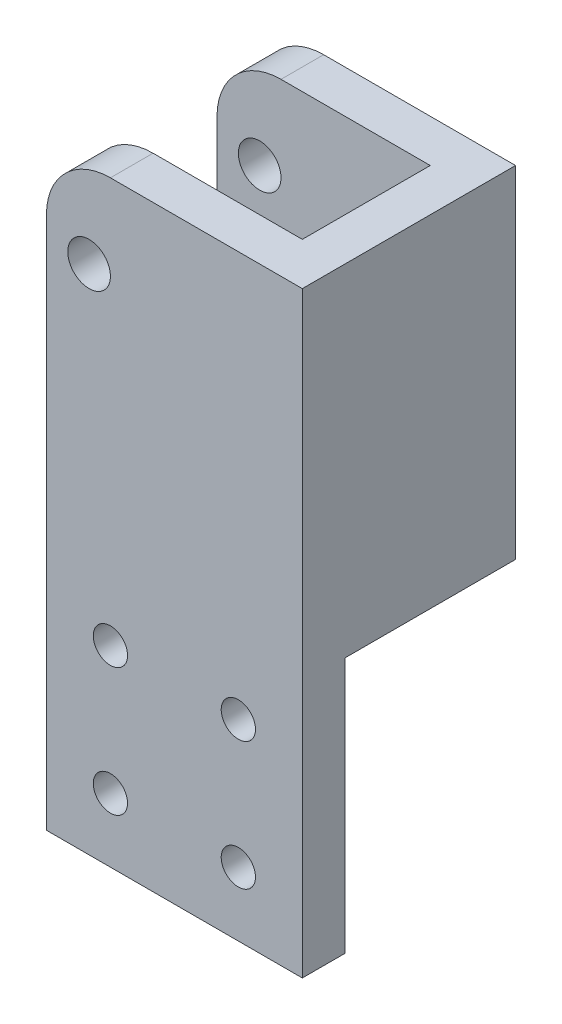
SolidWorks part; units mm, degrees
ref_plane "Front Plane" through (0, 0, 0) normal (0, 0, 1) x (1, 0, 0)
ref_plane "Top Plane" through (0, 0, 0) normal (0, 1, 0) x (1, 0, 0)
ref_plane "Right Plane" through (0, 0, 0) normal (1, 0, 0) x (0, 0, -1)
sketch "Sketch1" plane through (0, 0, 0) normal (0, 0, 1) x (1, 0, 0)
  line L1 (0, 0) -> (38.1, 0)
  line L2 (0, 0) -> (0, 76.2)
  line L3 (0, 76.2) -> (38.1, 76.2)
  line L4 (38.1, 0) -> (38.1, 76.2)
  dimension "D1" = 76.2
  dimension "D2" = 38.1
extrude "Boss-Extrude1" add sketch "Sketch1" against normal blind 31.75
sketch "Sketch2" plane through (0, 76.2, 0) normal (0, 1, 0) x (1, 0, 0)
  line L0 (0, 0) -> (0, 6.35)
  line L1 (0, 31.75) -> (0, 0) construction
  line L2 (0, 6.35) -> (31.75, 6.35)
  line L3 (31.75, 6.35) -> (31.75, 31.75)
  line L4 (38.1, 31.75) -> (0, 31.75) construction
  line L5 (38.1, 31.75) -> (38.1, 0) construction
  line L6 (31.75, 6.35) -> (31.75, 25.4) construction
  dimension "D1" = 6.35
  dimension "D2" = 6.35
  dimension "D3" = 19.05
sketch "Sketch3" plane through (0, 0, 0) normal (-1, 0, 0) x (0, 0, 1)
  line L0 (-31.75, 0) -> (-6.35, 0)
  line L1 (-31.75, 0) -> (0, 0) construction
  line L4 (-31.75, 0) -> (-31.75, 76.2)
  line L5 (-31.75, 76.2) -> (-6.35, 76.2)
  line L6 (-6.35, 0) -> (-6.35, 76.2)
  dimension "D1" = 25.4
  dimension "D2" = 76.2
extrude "Cut-Extrude2" cut sketch "Sketch3" against normal blind 31.75
sketch "Sketch4" plane through (31.75, 0, 0) normal (-1, 0, 0) x (0, 0, 1)
  line L0 (-6.35, 0) -> (-6.35, 76.2) construction
  line L1 (-31.75, 0) -> (-6.35, 0)
  line L2 (-31.75, 0) -> (-31.75, 25.4)
  line L3 (-31.75, 25.4) -> (-6.35, 25.4)
  line L4 (-6.35, 0) -> (-6.35, 25.4)
  dimension "D1" = 25.4
extrude "Cut-Extrude3" cut sketch "Sketch4" against normal through all
sketch "Sketch5" plane through (0, 76.2, 0) normal (0, 1, 0) x (1, 0, 0)
  line L0 (38.1, 31.75) -> (38.1, 0) construction
  line L1 (38.1, 0) -> (0, 0) construction
  line L2 (0, 0) -> (0, 6.35) construction
  line L3 (0, 6.35) -> (31.75, 6.35) construction
  line L4 (31.75, 6.35) -> (31.75, 31.75) construction
  line L5 (31.75, 31.75) -> (38.1, 31.75) construction
  line L6 (31.75, 6.35) -> (31.75, 25.4)
  line L7 (31.75, 31.75) -> (0, 31.75)
  line L8 (0, 31.75) -> (0, 25.4)
  line L9 (0, 25.4) -> (31.75, 25.4)
  line M6 (31.75, 31.75) -> (31.75, 6.35)
  dimension "D1" = 19.05
extrude "Boss-Extrude2" add sketch "Sketch5" against normal blind 50.8 contours L8 L9 L7 M6 region at (15.875, 76.2, -28.575)
sketch "Sketch6" plane through (0, 0, -31.75) normal (0, 0, -1) x (-1, 0, 0)
  line L0 (0, 76.2) -> (0, 63.5) construction
  line L1 (0, 25.4) -> (0, 76.2) construction
  line L2 (0, 63.5) -> (-6.35, 63.5) construction
  circle A0 centre (-6.35, 63.5) radius 3.175
  dimension "D3" = 6.35
  dimension "D1" = 12.7
  dimension "D2" = 6.35
extrude "Cut-Extrude4" cut sketch "Sketch6" against normal blind 50.8
fillet "Fillet2" radius 9.525 2 edges at (0, 76.2, -3.175) (0, 76.2, -28.575)
ref_plane "Plane1" through (0, 25.4, 0) normal (0, -1, 0) x (-1, 0, 0)
sketch "Sketch7" plane through (0, 25.4, 0) normal (0, -1, 0) x (-1, 0, 0)
  line L1 (0, 25.4) -> (-31.75, 25.4)
  line L2 (0, 25.4) -> (0, 6.35)
  line L3 (0, 6.35) -> (-31.75, 6.35)
  line L4 (-31.75, 25.4) -> (-31.75, 6.35)
extrude "Boss-Extrude3" add sketch "Sketch7" against normal blind 6.35
sketch "Sketch11" plane through (0, 0, 0) normal (0, -1, 0) x (1, 0, 0)
  line L1 (0, -6.35) -> (38.1, -6.35)
  line L2 (0, -6.35) -> (0, 0)
  line L3 (0, 0) -> (38.1, 0)
  line L4 (38.1, -6.35) -> (38.1, 0)
extrude "Boss-Extrude4" add sketch "Sketch11" along normal blind 12.7
sketch "Sketch8" plane through (0, 0, 0) normal (0, 0, 1) x (1, 0, 0)
  line L0 (0, -12.7) -> (0, 25.4) construction
  line L1 (0, 66.675) -> (0, -12.7) construction
  line L2 (0, 25.4) -> (38.1, 25.4) construction
  line L3 (38.1, -12.7) -> (38.1, 76.2) construction
  line L4 (38.1, 25.4) -> (38.1, -12.7) construction
  line L5 (38.1, -12.7) -> (0, -12.7) construction
  point P0 (9.525, 15.875)
  point P1 (28.575, 15.875)
  point P28 (9.525, -3.175)
  point P33 (28.575, -3.175)
  dimension "D4" = 9.525
  dimension "D5" = 9.525
  dimension "D6" = 9.525
  dimension "D1" = 38.1
  dimension "D2" = 9.525
  dimension "D3" = 9.525
  dimension "D7" = 9.525
  dimension "D8" = 9.525
  dimension "D9" = 9.525
hole_wizard "1/4-20 Tapped Hole2" positions "3DSketch2" profile "Sketch10" tap size "1/4-20" standard "ANSI Inch"
sketch3d "3DSketch2"
  point P9 (9.525, -3.175, 0)
  point P12 (28.575, -3.175, 0)
  point P19 (9.525, 15.875, 0)
  point P22 (28.575, 15.875, 0)
sketch "Sketch10" plane through (9.525, -3.175, 0) normal (1, 0, 0) x (0, -1, 0)
  line L0 (0, 0) -> (0, 18.0438)
  line L1 (0, 18.0438) -> (2.5527, 16.51)
  line L2 (2.5527, 16.51) -> (2.5527, 0)
  line L5 (2.5527, 0) -> (0, 0)
  line L10 (0, 18.0438) -> (-2.5527, 16.51) construction
  line L11 (0, -6.35) -> (0, 107.95) construction
  dimension "Tap Drill Dia." = 5.1054
  dimension "Tap Drill Depth" = 16.51
  dimension "Drill Angle" = 118
